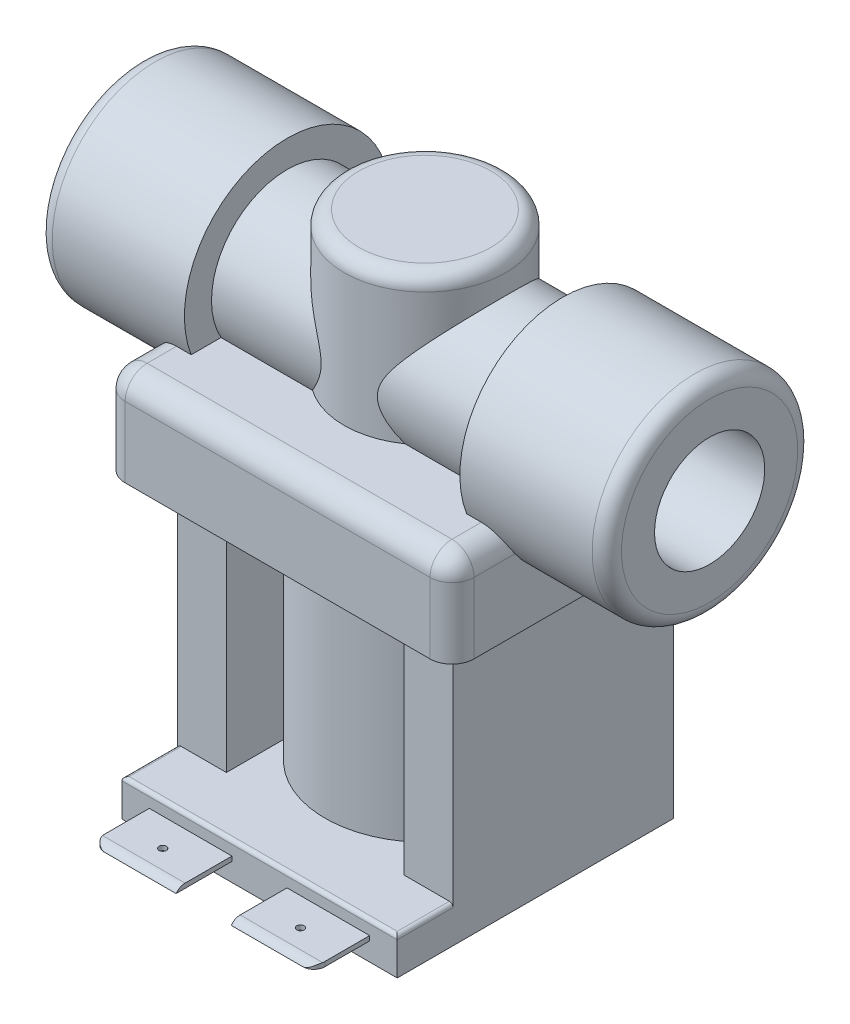
SolidWorks part; units mm, degrees
ref_plane "Front Plane" through (0, 0, 0) normal (0, 0, 1) x (1, 0, 0)
ref_plane "Top Plane" through (0, 0, 0) normal (0, 1, 0) x (1, 0, 0)
ref_plane "Right Plane" through (0, 0, 0) normal (1, 0, 0) x (0, 0, -1)
sketch "Sketch1" plane through (0, 0, 0) normal (0, 0, 1) x (1, 0, 0)
  line L1 (0, 0) -> (19.05, 0)
  line L2 (0, 0) -> (0, 19.05)
  line L3 (0, 19.05) -> (19.05, 19.05)
  line L4 (19.05, 0) -> (19.05, 19.05)
  dimension "D1" = 19.05
  dimension "D2" = 19.05
extrude "Boss-Extrude1" add sketch "Sketch1" along normal blind 15.24
sketch "Sketch2" plane through (0, 0, 15.24) normal (0, 0, 1) x (1, 0, 0)
  line L0 (19.05, 0) -> (19.05, 19.05) construction
  line L1 (0, 0) -> (19.05, 0)
  line L2 (0, 0) -> (0, 2.54)
  line L3 (0, 2.54) -> (19.05, 2.54)
  line L4 (19.05, 0) -> (19.05, 2.54)
  dimension "D1" = 2.54
extrude "Boss-Extrude2" add sketch "Sketch2" along normal blind 3.8608
sketch "Sketch3" plane through (0, 0, 19.1008) normal (0, 0, 1) x (1, 0, 0)
  line L0 (0, 1.27) -> (19.05, 1.27) construction
  line L1 (0, 2.54) -> (0, 0) construction
  line L2 (19.05, 0) -> (19.05, 2.54) construction
  line L3 (9.525, 2.54) -> (9.525, 0) construction
  line L4 (19.05, 2.54) -> (0, 2.54) construction
  line L5 (0, 0) -> (19.05, 0) construction
  line L6 (11.43, 1.27) -> (11.43, 1.5875)
  line L7 (7.62, 1.27) -> (1.905, 1.27)
  line L8 (7.62, 1.27) -> (7.62, 1.5875)
  line L9 (7.62, 1.5875) -> (1.905, 1.5875)
  line L10 (1.905, 1.27) -> (1.905, 1.5875)
  line L11 (17.145, 1.27) -> (17.145, 1.5875)
  line L12 (11.43, 1.27) -> (17.145, 1.27)
  line L13 (11.43, 1.5875) -> (17.145, 1.5875)
  dimension "D1" = 1.905
  dimension "D2" = 1.905
extrude "Boss-Extrude3" add sketch "Sketch3" along normal blind 3.8608
sketch "Sketch4" plane through (0, 1.5875, 0) normal (0, 1, 0) x (1, 0, 0)
  line L0 (7.62, -21.0312) -> (1.905, -21.0312) construction
  line L1 (7.62, -22.9616) -> (7.62, -19.1008) construction
  line L2 (1.905, -22.9616) -> (1.905, -19.1008) construction
  line L3 (11.43, -21.0312) -> (17.145, -21.0312) construction
  line L4 (11.43, -22.9616) -> (11.43, -19.1008) construction
  line L5 (17.145, -22.9616) -> (17.145, -19.1008) construction
  circle A0 centre (4.7625, -21.0312) radius 0.254
  circle A1 centre (14.2875, -21.0312) radius 0.254
extrude "Cut-Extrude1" cut sketch "Sketch4" against normal blind 3.8608
sketch "Sketch5" plane through (0, 19.05, 0) normal (0, 1, 0) x (1, 0, 0)
  line L0 (3.3762, 0) -> (3.3762, -15.24)
  line L1 (19.05, 0) -> (0, 0) construction
  line L2 (19.05, -15.24) -> (0, -15.24) construction
  line L3 (9.525, 0) -> (9.525, -15.24) construction
  line L4 (15.6738, 0) -> (15.6738, -15.24)
  circle A0 centre (9.525, -7.62) radius 6.951
  line M3 (19.05, 0) -> (0, 0)
  line M5 (0, -15.24) -> (19.05, -15.24)
extrude "Cut-Extrude2" cut sketch "Sketch5" against normal blind 16.51 contours A0 L3 L4 M5 | L3 A0 L0 M5 | L3 L0 A0 M3 | L3 A0 L4 M3 region at (5.449, 19.05, 1.1746) region at (13.601, 19.05, 1.1746) region at (5.449, 19.05, 14.0654) region at (13.601, 19.05, 14.0654)
sketch "Sketch6" plane through (0, 0, 0) normal (-1, 0, 0) x (0, 0, 1)
  line L1 (0, 19.05) -> (15.3122, 19.05)
  line L2 (0, 19.05) -> (0, 35.56)
  line L3 (0, 35.56) -> (15.3122, 35.56)
  line L4 (15.3122, 19.05) -> (15.3122, 35.56)
  dimension "D1" = 16.51
  dimension "D2" = 15.3122
extrude "Boss-Extrude4" add sketch "Sketch6" along normal blind 10.16 and the other way blind 29.21
sketch "Sketch7" plane through (-10.16, 0, 0) normal (-1, 0, 0) x (0, 0, 1)
  line L0 (7.6561, 35.56) -> (7.6561, 19.05) construction
  line L1 (15.3122, 35.56) -> (0, 35.56) construction
  line L2 (0, 19.05) -> (15.3122, 19.05) construction
  circle A0 centre (7.6561, 27.94) radius 7.112
  dimension "D1" = 7.62
extrude "Cut-Extrude3" cut sketch "Sketch7" against normal blind 10.16 flip side to cut
sketch "Sketch8" plane through (29.21, 0, 0) normal (1, 0, 0) x (0, 0, -1)
  line L0 (-7.6561, 35.56) -> (-7.6561, 19.05) construction
  line L1 (-15.3122, 35.56) -> (0, 35.56) construction
  line L2 (0, 19.05) -> (-15.3122, 19.05) construction
  circle A0 centre (-7.6561, 27.94) radius 7.112
  dimension "D1" = 7.62
extrude "Cut-Extrude4" cut sketch "Sketch8" against normal blind 10.16 flip side to cut
sketch "Sketch9" plane through (0, 35.56, 0) normal (0, 1, 0) x (1, 0, 0)
  line L0 (9.525, 0) -> (9.525, -15.3122) construction
  line L1 (19.05, 0) -> (0, 0) construction
  line L2 (19.05, -15.3122) -> (0, -15.3122) construction
  line L4 (0, 0) -> (19.05, 0)
  line L5 (0, 0) -> (0, -15.3122)
  line L6 (0, -15.3122) -> (19.05, -15.3122)
  line L7 (19.05, 0) -> (19.05, -15.3122)
  circle A0 centre (9.525, -7.6561) radius 5.588
extrude "Cut-Extrude6" cut sketch "Sketch9" against normal blind 10.16
sketch "Sketch10" plane through (0, 0, 0) normal (1, 0, 0) x (0, 0, -1)
  line L0 (-7.6561, 27.94) -> (-8.6345, 34.9844) construction
  arc A0 (-1.0131, 25.4) -> (-14.2991, 25.4) centre (-7.6561, 27.94) ccw construction
  circle A1 centre (-7.6561, 27.94) radius 5.2384
extrude "Boss-Extrude5" add sketch "Sketch10" along normal blind 20.32
sketch "Sketch11" plane through (0, 0, 15.3122) normal (0, 0, 1) x (1, 0, 0)
  line L0 (19.05, 19.05) -> (19.05, 25.4) construction
  line L1 (0, 25.4) -> (21.59, 25.4)
  line L3 (0, 18.996) -> (21.59, 18.996)
  line L4 (21.59, 25.4) -> (21.59, 18.996)
  line L5 (0, 25.4) -> (-2.54, 25.4)
  line L6 (0, 25.4) -> (0, 18.996)
  line L7 (0, 18.996) -> (-2.54, 18.996)
  line L8 (-2.54, 25.4) -> (-2.54, 18.996)
  line M4 (19.05, 19.05) -> (19.05, 25.4)
  line M5 (19.05, 25.4) -> (0, 25.4)
  line M6 (0, 25.4) -> (0, 19.05)
  line M7 (0, 19.05) -> (19.05, 19.05)
  dimension "D2" = 2.54
extrude "Boss-Extrude6" add sketch "Sketch11" along normal blind 2.54 and the other way blind 17.78 contours M7 M4 M5 M6 | L5 L8 L7 L6 M6 | L6 L3 L4 L1 M7 M4 region at (-1.27, 22.198, 15.3122) region at (9.525, 22.225, 15.3122) region at (19.6783, 22.0093, 15.3122)
fillet "Fillet1" radius 1.524 10 edges at (-2.54, 25.4, -0.7273) (-2.54, 22.198, -2.4678) (9.525, 25.4, -2.4678) (21.59, 25.4, -0.7273) (21.59, 22.198, -2.4678) (21.59, 25.4, 16.0756) (21.59, 22.198, 17.8522) (-2.54, 22.198, 17.8522) (-2.54, 25.4, 16.0756) (9.525, 25.4, 17.8522)
fillet "Fillet2" radius 1.016 1 edges at (9.525, 35.56, 13.2441)
fillet "Fillet3" radius 1.016 2 edges at (29.21, 27.94, 0.5441) (-10.16, 27.94, 14.7681)
fillet "Fillet5" radius 0.762 4 edges at (17.145, 1.4288, 22.9616) (14.2875, 1.5875, 22.9616) (1.905, 1.4288, 22.9616) (4.7625, 1.5875, 22.9616)
fillet "Fillet6" radius 0.254 4 edges at (9.525, 2.54, 0) (19.05, 2.54, 17.1704) (0, 2.54, 17.1704) (9.525, 2.54, 19.1008)
sketch "Sketch12" plane through (-10.16, 0, 0) normal (-1, 0, 0) x (0, 0, 1)
  circle A0 centre (7.6561, 27.94) radius 3.81
extrude "Cut-Extrude7" cut sketch "Sketch12" against normal through all
